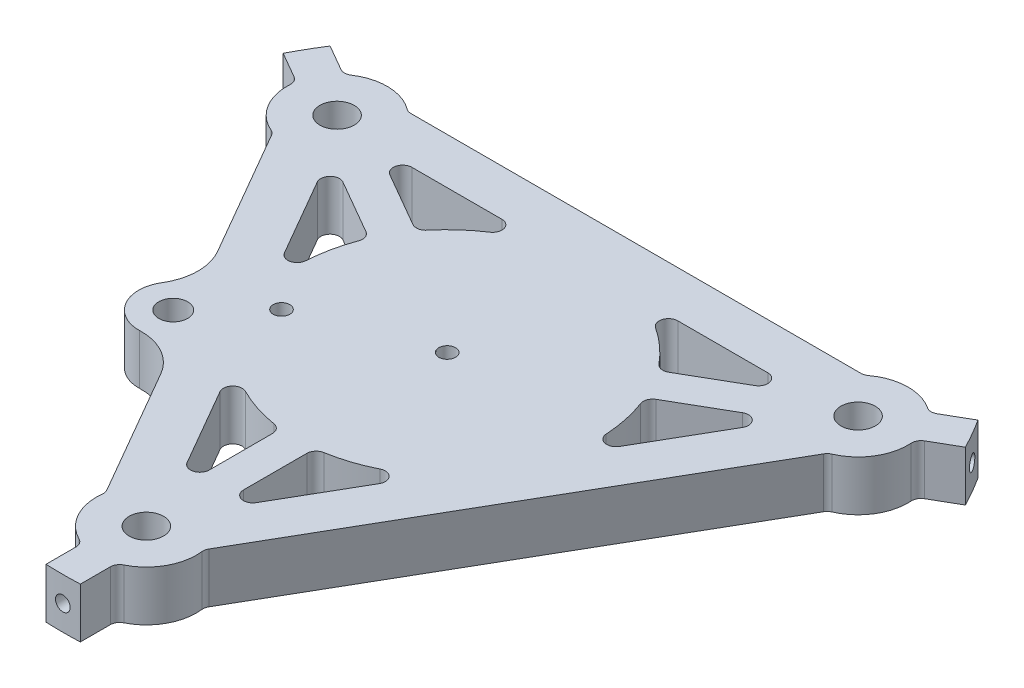
SolidWorks part; units mm, degrees
material "ABS"
ref_plane "Front Plane" through (0, 0, 0) normal (0, 0, 1) x (1, 0, 0)
ref_plane "Top Plane" through (0, 0, 0) normal (0, 1, 0) x (1, 0, 0)
ref_plane "Right Plane" through (0, 0, 0) normal (1, 0, 0) x (0, 0, -1)
sketch "Sketch1" plane through (0, 0, 0) normal (0, 1, 0) x (1, 0, 0)
  line L0 (-3.2639, -67.2662) -> (-3.2639, -72.952)
  line L1 (3.2639, -67.2662) -> (3.2639, -72.952)
  line L2 (3.2639, -41.9471) -> (3.2639, -29.9313)
  line L3 (-3.2639, -41.9471) -> (-3.2639, -29.9313)
  line L4 (-34.6953, 23.8002) -> (-24.2893, 17.7923)
  line L5 (-37.9592, 18.1469) -> (-27.5532, 12.139)
  line L6 (-56.6223, 36.4597) -> (-61.5464, 39.3026)
  line L7 (-59.8862, 30.8065) -> (-64.8103, 33.6494)
  line L8 (37.9592, 18.1469) -> (27.5532, 12.139)
  line L9 (34.6953, 23.8002) -> (24.2893, 17.7923)
  line L10 (59.8862, 30.8065) -> (64.8103, 33.6494)
  line L11 (56.6223, 36.4597) -> (61.5464, 39.3026)
  line L12 (0, 0) -> (0, -57.15) construction
  line L13 (0, 0) -> (-49.4934, 28.575) construction
  line L14 (0, 0) -> (49.4934, 28.575) construction
  line L15 (40.388, 15.7181) -> (31.8393, 0.9115)
  line L16 (9.6892, -54.9694) -> (52.4495, 19.0936)
  line L17 (-6.5817, -42.8361) -> (-15.1303, -28.0294)
  line L18 (-52.4495, 19.0936) -> (-9.6892, -54.9694)
  line L19 (-42.7603, 35.8758) -> (42.7603, 35.8758)
  line L20 (-33.8063, 27.118) -> (-16.709, 27.118)
  line L21 (16.709, 27.118) -> (33.8063, 27.118)
  line L22 (-31.8393, 0.9115) -> (-40.388, 15.7181)
  line L23 (15.1303, -28.0294) -> (6.5817, -42.8361)
  arc A0 (-3.2639, -72.952) -> (3.2639, -72.952) centre (0, 0) ccw
  arc A1 (4.7466, -28.178) -> (12.7944, -25.5506) centre (0, 0) ccw
  arc A2 (-9.4626, -56.0616) -> (-4.2488, -65.6749) centre (0, -57.15) ccw
  circle A3 centre (0, -57.15) radius 3.2639
  arc A4 (4.2488, -65.6749) -> (9.4626, -56.0616) centre (0, -57.15) ccw
  arc A5 (-43.8195, 36.2257) -> (-54.7517, 36.517) centre (-49.4934, 28.575) ccw
  arc A6 (-61.5464, 39.3026) -> (-64.8103, 33.6494) centre (0, 0) ccw
  arc A7 (-59.0005, 29.1579) -> (-53.2821, 19.8359) centre (-49.4934, 28.575) ccw
  circle A8 centre (-49.4934, 28.575) radius 3.2639
  arc A9 (53.2821, 19.8359) -> (59.0005, 29.1579) centre (49.4934, 28.575) ccw
  arc A10 (64.8103, 33.6494) -> (61.5464, 39.3026) centre (0, 0) ccw
  arc A11 (54.7517, 36.517) -> (43.8195, 36.2257) centre (49.4934, 28.575) ccw
  circle A12 centre (49.4934, 28.575) radius 3.2639
  arc A13 (-26.7762, 9.9784) -> (-28.5247, 1.695) centre (0, 0) ccw
  arc A14 (22.0296, 18.1997) -> (15.7302, 23.8556) centre (0, 0) ccw
  circle A15 centre (0, 0) radius 1.5875
  arc A16 (-12.7944, -25.5506) -> (-4.7466, -28.178) centre (0, 0) ccw
  arc A17 (28.5247, 1.695) -> (26.7762, 9.9784) centre (0, 0) ccw
  arc A18 (-15.7302, 23.8556) -> (-22.0296, 18.1997) centre (0, 0) ccw
  arc A19 (37.9592, 18.1469) -> (40.388, 15.7181) centre (38.8482, 16.6071) cw
  arc A20 (26.7762, 9.9784) -> (27.5532, 12.139) centre (28.4422, 10.5992) cw
  arc A21 (3.2639, -29.9313) -> (4.7466, -28.178) centre (5.0419, -29.9313) cw
  arc A22 (15.1303, -28.0294) -> (12.7944, -25.5506) centre (13.5905, -27.1404) ccw
  arc A23 (6.5817, -42.8361) -> (3.2639, -41.9471) centre (5.0419, -41.9471) cw
  arc A24 (-6.5817, -42.8361) -> (-3.2639, -41.9471) centre (-5.0419, -41.9471) ccw
  arc A25 (-3.2639, -29.9313) -> (-4.7466, -28.178) centre (-5.0419, -29.9313) ccw
  arc A26 (-15.1303, -28.0294) -> (-12.7944, -25.5506) centre (-13.5905, -27.1404) cw
  arc A27 (-31.8393, 0.9115) -> (-28.5247, 1.695) centre (-30.2996, 1.8005) ccw
  arc A28 (-26.7762, 9.9784) -> (-27.5532, 12.139) centre (-28.4422, 10.5992) ccw
  arc A29 (-40.388, 15.7181) -> (-37.9592, 18.1469) centre (-38.8482, 16.6071) cw
  arc A30 (-24.2893, 17.7923) -> (-22.0296, 18.1997) centre (-23.4003, 19.3321) ccw
  arc A31 (-34.6953, 23.8002) -> (-33.8063, 27.118) centre (-33.8063, 25.34) cw
  arc A32 (-15.7302, 23.8556) -> (-16.709, 27.118) centre (-16.709, 25.34) ccw
  arc A33 (-4.2488, -65.6749) -> (-3.2639, -67.2662) centre (-5.0419, -67.2662) cw
  arc A34 (3.2639, -67.2662) -> (4.2488, -65.6749) centre (5.0419, -67.2662) cw
  arc A35 (9.6892, -54.9694) -> (9.4626, -56.0616) centre (11.229, -55.8584) ccw
  arc A36 (-9.4626, -56.0616) -> (-9.6892, -54.9694) centre (-11.229, -55.8584) ccw
  arc A37 (-52.4495, 19.0936) -> (-53.2821, 19.8359) centre (-53.9893, 18.2046) ccw
  arc A38 (-59.0005, 29.1579) -> (-59.8862, 30.8065) centre (-60.7752, 29.2667) ccw
  arc A39 (-56.6223, 36.4597) -> (-54.7517, 36.517) centre (-55.7333, 37.9995) ccw
  arc A40 (-43.8195, 36.2257) -> (-42.7603, 35.8758) centre (-42.7603, 37.6538) ccw
  arc A41 (42.7603, 35.8758) -> (43.8195, 36.2257) centre (42.7603, 37.6538) ccw
  arc A42 (52.4495, 19.0936) -> (53.2821, 19.8359) centre (53.9893, 18.2046) cw
  arc A43 (54.7517, 36.517) -> (56.6223, 36.4597) centre (55.7333, 37.9995) ccw
  arc A44 (59.0005, 29.1579) -> (59.8862, 30.8065) centre (60.7752, 29.2667) cw
  arc A45 (15.7302, 23.8556) -> (16.709, 27.118) centre (16.709, 25.34) cw
  arc A46 (34.6953, 23.8002) -> (33.8063, 27.118) centre (33.8063, 25.34) ccw
  arc A47 (22.0296, 18.1997) -> (24.2893, 17.7923) centre (23.4003, 19.3321) ccw
  arc A48 (31.8393, 0.9115) -> (28.5247, 1.695) centre (30.2996, 1.8005) cw
  point P53 (18.9808, -21.3603)
  point P64 (-27.9889, -5.7577)
  point P77 (-3.2639, -66.0983)
  point P80 (3.2639, -66.0983)
  point P103 (9.0082, 27.118)
  dimension "D1" = 146.05
  dimension "D2" = 57.15
  dimension "D3" = 19.05
  dimension "D4" = 6.5278
  dimension "D9" = 3.175
  dimension "D10" = 1.778
  dimension "D11" = 1.778
  dimension "D5" = 57.15
  dimension "D7" = 120
  dimension "D8" = 120
  dimension "D6" = 3
extrude "Boss-Extrude1" add sketch "Sketch1" along normal mid plane 9.525
sketch "Sketch2" plane through (0, 0, 0) normal (0, 0, 1) x (1, 0, 0)
  line L0 (0, 4.7625) -> (0, -4.7625) construction
  line L1 (3.2639, 4.7625) -> (-3.2639, 4.7625) construction
  line L2 (-3.2639, -4.7625) -> (3.2639, -4.7625) construction
ref_plane "Plane1" through (0, 0, 73.025) normal (0, 0, 1) x (1, 0, 0)
sketch "Sketch3" plane through (0, 0, 73.025) normal (0, 0, 1) x (1, 0, 0)
  circle A0 centre (0, 0) radius 1.397
  dimension "D1" = 2.794
extrude "Cut-Extrude1" cut sketch "Sketch3" against normal blind 6.35
pattern_circular "CirPattern1" count 3 over 360 about axis through (0, 4.7625, 0) along (0, -1, 0) of "Cut-Extrude1"
sketch "Sketch4" plane through (0, -4.7625, 0) normal (0, -1, 0) x (1, 0, 0)
  circle A0 centre (-22.821, 8.6514) radius 1.5875
  dimension "D1" = 3.175
extrude "Cut-Extrude2" cut sketch "Sketch4" against normal through all both and the other way through all
sketch "Sketch5" plane through (0, 4.7625, 0) normal (0, 1, 0) x (1, 0, 0)
  line L0 (0, 0) -> (-32.9956, -19.05)
  line L1 (-52.4495, 19.0936) -> (-9.6892, -54.9694) construction
  line L2 (-52.4495, 19.0936) -> (-9.6892, -54.9694)
  circle A0 centre (-32.9956, -19.05) radius 2.75
  circle A1 centre (-32.9956, -19.05) radius 6.56
  dimension "D2" = 5.5
  dimension "D1" = 38.1
  dimension "D3" = 3.81
extrude "Boss-Extrude2" add sketch "Sketch5" against normal up to surface (9.525 mm away) contours L2 A1 A0 region at (-33.1673, 4.7625, 14.6524) up to face at (-22.821, -4.7625, 10.2389)
extrude "Cut-Extrude3" cut sketch "Sketch5<3>" against normal through all contours L2 A0 L0 | L0 A0 L2 region at (-30.5781, 4.7625, 18.3644) region at (-31.1931, 4.7625, 17.2992)
sketch "Sketch5<3>" plane through (0, 4.7625, 0) normal (0, 1, 0) x (1, 0, 0) same geometry as "Sketch5"
fillet "Fillet2" radius 10.16 2 edges at (-34.1551, 0, 12.5933) (-27.9836, 0, 23.2825)
equation "\"Bodytube_OD\" = 6.17in"
equation "\"Bodytube_ID\" = 5.998in"
equation "\"Motor_OD\" = 4in"
equation "\"Fwd_Tube_Length\" = 40in"
equation "\"Mid_Tube_Length\" = 1in"
equation "\"Aft_Section_Length\"= 39in"
equation "\"Mid_Coupler_Length\"= 13in"
equation "\"Aft_Lower_Length\"= 22in"
equation "\"AB_Coupler_OD_Length\"= 1in"
equation "\"AB_Coupling_Section_Length\"= 0.375in"
equation "\"AB_Coupler_Length\"= \"AB_Coupler_OD_Length\" + \"AB_Coupling_Section_Length\" * 2"
equation "\"Cutout_Angle\" = 80"
equation "\"AB_Paddle_Height\" = 0.375in"
equation "\"AB_Coupler_Num_Screws\"= 6"
equation "\"Num_Cutouts\" = 3"
equation "\"AB_Coupler_OD\"= 6.17in"
equation "\"AB_Coupler_ID\"= 5.75in"
equation "\"AB_Coupler_Surface_Diameter\"= 5.998in"
equation "\"AB_Coupling_Screw_Diameter\"= 0.1065in"
equation "\"AB_Central_Bushing_Length\" = .75in"
equation "\"Lead_Screw_Dist\" = 2.25in"
equation "\"Lead_Screw_Diam\" = (27/64)*1in"
equation "\"Lead_Screw_Length\" = (\"Mid_Coupler_Length\" + 2*0.375in + 2*0.5in)"
equation "\"Paddle_Pin_Offset\" = .25in"
equation "\"Paddle_Pin_Radius\" = 2.25in"
equation "\"Paddle_Gear_OD\" = 3.2in"
equation "\"Fwd_BKHD_From_Top\" = 18in"
equation "\"Fin_Thickness\"= .118in"
equation "\"Guiderail_Cutout_Diameter\"= 1.5in"
equation "\"D5@Sketch1\"=\"Paddle_Pin_Radius\""
